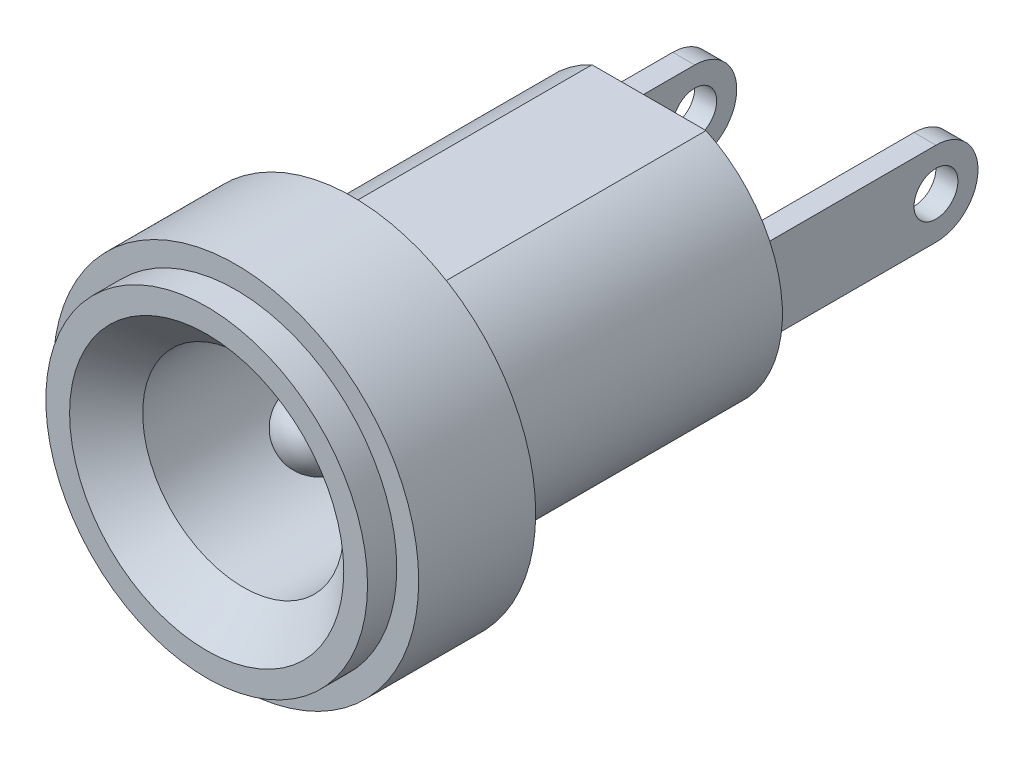
SolidWorks part; units mm, degrees
ref_plane "Plan de face" through (0, 0, 0) normal (0, 0, 1) x (1, 0, 0)
ref_plane "Plan de dessus" through (0, 0, 0) normal (0, 1, 0) x (1, 0, 0)
ref_plane "Plan de droite" through (0, 0, 0) normal (1, 0, 0) x (0, 0, -1)
sketch "Esquisse1" plane through (0, 0, 0) normal (0, 0, 1) x (1, 0, 0)
  line L0 (-1.5596, 3.3) -> (1.5596, 3.3)
  line L2 (1.5596, -3.3) -> (-1.5596, -3.3)
  circle A0 centre (0, 0) radius 5
  circle A1 centre (0, 0) radius 4.4
  arc A2 (-1.5596, 3.3) -> (-1.5596, -3.3) centre (0, 0) ccw
  circle A3 centre (0, 0) radius 2.75
  circle A4 centre (0, 0) radius 0.95
  arc A5 (1.5596, -3.3) -> (1.5596, 3.3) centre (0, 0) ccw
  dimension "D1" = 10
  dimension "D2" = 8.8
  dimension "D3" = 7.3
  dimension "D4" = 5.5
  dimension "D5" = 1.9
  dimension "D6" = 6.6
extrude "Boss.-Extru.1" add sketch "Esquisse1" along normal blind 3.2 contours A0
extrude "Boss.-Extru.2" add sketch "Esquisse1<3>" along normal blind 0.8 from surface contours A1 starting at face at (5, 0, 3.2)
sketch "Esquisse1<3>" plane through (0, 0, 0) normal (0, 0, 1) x (1, 0, 0) same geometry as "Esquisse1"
extrude "Boss.-Extru.3" add sketch "Esquisse1<4>" against normal blind 8.1 contours A2 L2 A5 L0
sketch "Esquisse1<4>" plane through (0, 0, 0) normal (0, 0, 1) x (1, 0, 0) same geometry as "Esquisse1"
extrude "Enlèv. mat.-Extru.1" cut sketch "Esquisse1<5>" against normal blind 9 from surface contours A3 starting at face at (4.4, 0, 4)
sketch "Esquisse1<5>" plane through (0, 0, 0) normal (0, 0, 1) x (1, 0, 0) same geometry as "Esquisse1"
extrude "Boss.-Extru.4" add sketch "Esquisse1<6>" along normal offset from surface (6.9 mm away) 2.1 from surface contours A4 up to face at (2.75, 0, 4) starting at face at (2.75, 0, -5)
sketch "Esquisse1<6>" plane through (0, 0, 0) normal (0, 0, 1) x (1, 0, 0) same geometry as "Esquisse1"
chamfer "Chanfrein1" distance 1 angle 45 1 edges at (2.75, 0, 4)
fillet "Congé1" radius 0.95 1 edges at (0.95, 0, 1.9)
sketch "Esquisse2" plane through (0, 0, -8.1) normal (0, 0, -1) x (-1, 0, 0)
  line L0 (0, 0) -> (2.3, 0) construction
  line L1 (2.3, 1.15) -> (2.9, 1.15)
  line L2 (2.3, 1.15) -> (2.3, -1.15)
  line L3 (2.3, -1.15) -> (2.9, -1.15)
  line L4 (2.9, 1.15) -> (2.9, -1.15)
  line L5 (0, 5.5) -> (0, -5.5) construction
  line L6 (-2.3, 1.15) -> (-2.3, -1.15)
  line L7 (-2.3, -1.15) -> (-2.9, -1.15)
  line L8 (-2.9, 1.15) -> (-2.9, -1.15)
  line L9 (-2.3, 1.15) -> (-2.9, 1.15)
  dimension "D1" = 0.6
  dimension "D2" = 2.3
  dimension "D3" = 2.3
extrude "Boss.-Extru.5" add sketch "Esquisse2" along normal blind 6.1 contours L6 L7 L8 L9
extrude "Boss.-Extru.6" add sketch "Esquisse2<3>" along normal blind 4.7 contours L1 L4 L3 L2
sketch "Esquisse2<3>" plane through (0, 0, -8.1) normal (0, 0, -1) x (-1, 0, 0) same geometry as "Esquisse2"
fillet "Congé2" radius 1.15 4 edges at (-2.6, -1.15, -12.8) (-2.6, 1.15, -12.8) (2.6, -1.15, -14.2) (2.6, 1.15, -14.2)
sketch "Esquisse3" plane through (2.3, 0, 0) normal (-1, 0, 0) x (0, 0, 1)
  circle A0 centre (-13.05, 0) radius 0.6
  dimension "D1" = 1.2
extrude "Enlèv. mat.-Extru.2" cut sketch "Esquisse3" against normal up to next
sketch "Esquisse4" plane through (-2.9, 0, 0) normal (-1, 0, 0) x (0, 0, 1)
  circle A0 centre (-11.65, 0) radius 0.6
  circle A1 centre (-13.05, 0) radius 0.6 construction
extrude "Enlèv. mat.-Extru.3" cut sketch "Esquisse4" against normal up to next
